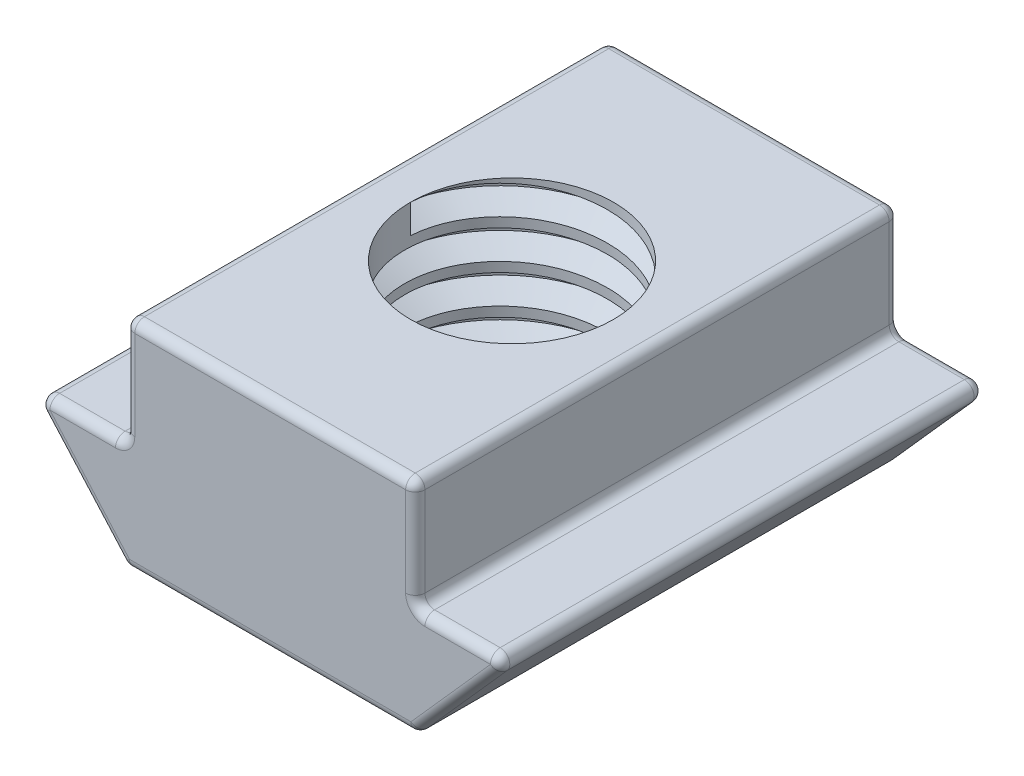
SolidWorks part; units mm, degrees
ref_plane "Ön Düzlem" through (0, 0, 0) normal (0, 0, 1) x (1, 0, 0)
ref_plane "Üst Düzlem" through (0, 0, 0) normal (0, 1, 0) x (1, 0, 0)
ref_plane "Sağ Düzlem" through (0, 0, 0) normal (1, 0, 0) x (0, 0, -1)
sketch "Çizim1" plane through (0, 0, 0) normal (0, 0, 1) x (1, 0, 0)
  line L0 (3, 0) -> (-3, 0)
  line L1 (-3, 0) -> (-3, -2.25)
  line L2 (-3, -2.25) -> (-5, -2.25)
  line L5 (-3, -4.5) -> (-5, -2.25)
  line L6 (-3, -4.5) -> (3, -4.5)
  line L7 (0, 0) -> (0, -3.1473) construction
  line L8 (3, -4.5) -> (5, -2.25)
  line L9 (3, -2.25) -> (5, -2.25)
  line L10 (3, 0) -> (3, -2.25)
  point P10 (0, -4.5)
  point P13 (0, 0)
  dimension "D4" = 6
  dimension "D1" = 3
  dimension "D2" = 2.25
  dimension "D3" = 2
extrude "Yükseklik-Ekstrüzyon1" add sketch "Çizim1" along normal blind 10
sketch "Çizim2" plane through (0, 0, 0) normal (0, 1, 0) x (1, 0, 0)
  circle A0 centre (0, -5) radius 2.1
  dimension "D2" = 4.2
extrude "Kes-Ekstrüzyon1" cut sketch "Çizim2" against normal through all
thread "Diş1" pitch 0.8 method cut profile "Diş Profili1" start angle 0, offset 0, length 5, pitch 0.8, diameter 4.2
ref_plane "Düzlem1" through (-2.1, 0, 5) normal (0, 0, 1) x (-1, 0, 0)
sketch "Diş Profili1" plane through (-2.1, 0, 5) normal (0, 0, 1) x (-1, 0, 0)
  line L0 (0, 0) -> (0, 0.8) construction
  line L1 (0, 0) -> (0.433, 0.25)
  line L2 (0.433, 0.25) -> (0.433, 0.35)
  line L3 (0.433, 0.35) -> (0, 0.6)
  line L4 (0.433, 0.3) -> (0, 0.3) construction
  line L11 (0, 0) -> (0, 0.6)
  point P2 (0, 0)
  dimension "Pitch" = 0.8
  dimension "Profile_Angle" = 60
  dimension "Profile_Land" = 0.1
  dimension "Profile_Height" = 0.433
fillet "Radyus1" radius 0.2 24 edges at (-3, -2.25, 5) (-5, -2.25, 5) (-3, -4.5, 5) (0, -4.5, 10) (-4, -3.375, 10) (-3, -1.125, 10) (-4, -2.25, 10) (-3, 0, 5) (-3, -1.125, 0) (-4, -2.25, 0) (-4, -3.375, 0) (4, -3.375, 0) (0, -4.5, 0) (3, -4.5, 5) (4, -3.375, 10) (4, -2.25, 10) (3, -1.125, 10) (4, -2.25, 0) (3, -2.25, 5) (3, -1.125, 0) (0, 0, 10) (0, 0, 0) (3, 0, 5) (5, -2.25, 5)
